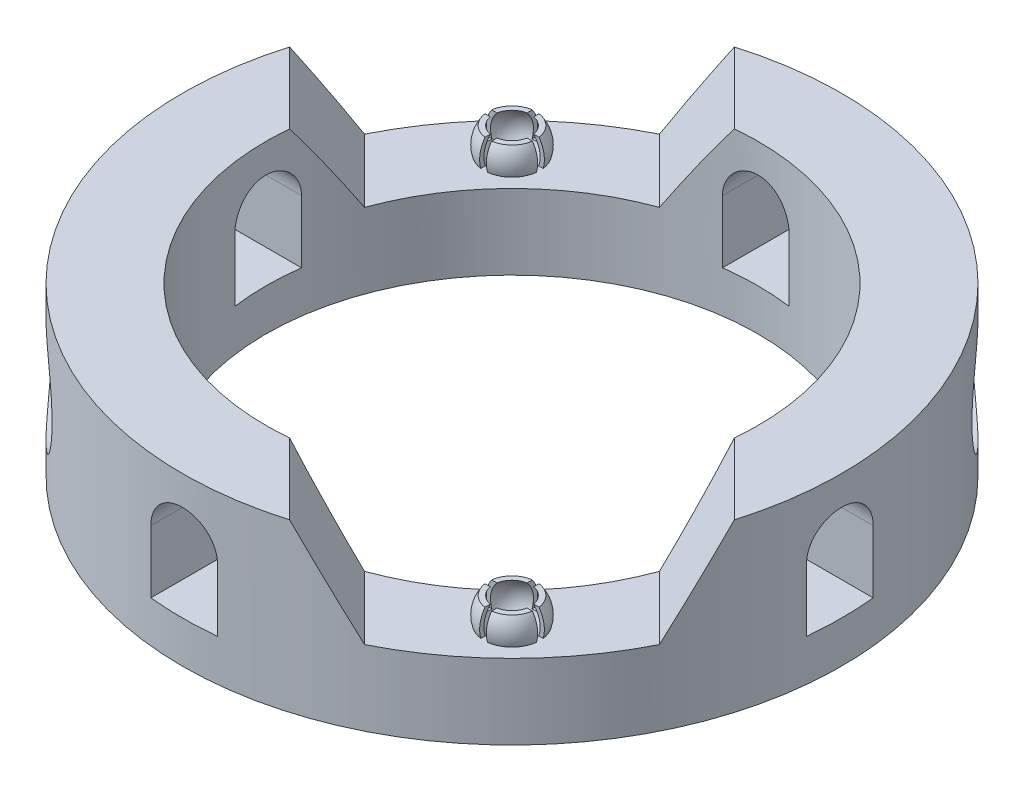
SolidWorks part; units mm, degrees
ref_plane "Front Plane" through (0, 0, 0) normal (0, 0, 1) x (1, 0, 0)
ref_plane "Top Plane" through (0, 0, 0) normal (0, 1, 0) x (1, 0, 0)
ref_plane "Right Plane" through (0, 0, 0) normal (1, 0, 0) x (0, 0, -1)
sketch "Sketch1" plane through (0, 0, 0) normal (0, 1, 0) x (1, 0, 0)
  circle A0 centre (0, 0) radius 29.5
  circle A1 centre (0, 0) radius 39.5
  dimension "D1" = 59
  dimension "D2" = 79
extrude "Boss-Extrude1" add sketch "Sketch1" along normal blind 20
ref_plane "Plane1" through (0, 0, 0) normal (0.7071, 0, -0.7071) x (-0.7071, 0, -0.7071)
sketch "Sketch2" plane through (0, 0, 0) normal (1, 0, 0) x (0, 0, -1)
  line L0 (0, 0) -> (0, 30.0667) construction
  line L1 (4, 5) -> (-4, 5)
  line L2 (-4, 5) -> (-4, 12.5)
  line L3 (4, 5) -> (4, 12.5)
  arc A0 (-4, 12.5) -> (4, 12.5) centre (0, 12.5) cw
  dimension "D6" = 4
  dimension "D1" = 8
  dimension "D2" = 4
  dimension "D3" = 5
  dimension "D4" = 7.5
  dimension "D5" = 7.5
extrude "Cut-Extrude1" cut sketch "Sketch2" against normal through all
extrude "Cut-Extrude2" cut sketch "Sketch2<2>" along normal through all
sketch "Sketch2<2>" plane through (0, 0, 0) normal (1, 0, 0) x (0, 0, -1) same geometry as "Sketch2"
mirror "Mirror1" about plane through (0, 0, 0) normal (0.7071, 0, -0.7071) of "Cut-Extrude2", "Cut-Extrude1"
sketch "Sketch4" plane through (0, 0, 0) normal (0.7071, 0, -0.7071) x (-0.7071, 0, -0.7071)
  line L0 (0, 0) -> (0, 44.1067) construction
  circle A0 centre (0, 10) radius 3.175
  dimension "D1" = 6.35
  dimension "D2" = 10
extrude "Cut-Extrude3" cut sketch "Sketch4" against normal up to next
extrude "Cut-Extrude4" cut sketch "Sketch4<2>" along normal up to next
sketch "Sketch4<2>" plane through (0, 0, 0) normal (0.7071, 0, -0.7071) x (-0.7071, 0, -0.7071) same geometry as "Sketch4"
ref_plane "Plane2" through (0, 0, 0) normal (0.7071, 0, 0.7071) x (0.7071, 0, -0.7071)
sketch "Sketch5" plane through (0, 20, 0) normal (0, 1, 0) x (1, 0, 0)
  line L0 (13.6827, -13.6827) -> (-13.6827, 13.6827) construction
  line L1 (-27.9307, 27.9307) -> (27.9307, -27.9307) construction
  line L2 (25.4558, -28.9914) -> (28.9914, -25.4558)
  line L3 (25.4558, -28.9914) -> (19.799, -23.3345)
  line L4 (28.9914, -25.4558) -> (23.3345, -19.799)
  line L5 (19.799, -23.3345) -> (23.3345, -19.799)
  line L6 (25.4558, -28.9914) -> (23.3345, -19.799) construction
  line L7 (28.9914, -25.4558) -> (19.799, -23.3345) construction
  circle A0 centre (0, 0) radius 39.5 construction
  circle A1 centre (0, 0) radius 29.5 construction
  point P7 (24.3952, -24.3952)
  dimension "D1" = 34.5
  dimension "D2" = 8
  dimension "D3" = 5
extrude "Boss-Extrude2" add sketch "Sketch5" along normal blind 13
sketch "Sketch6" plane through (1.7678, 0, -1.7678) normal (0.7071, 0, -0.7071) x (-0.7071, 0, -0.7071)
  line L0 (-38.5, 33) -> (-38.5, 20) construction
  line L1 (-38.5, 33) -> (-30.5, 33) construction
  line L2 (-30.5, 33) -> (-30.5, 20) construction
  line L4 (-38.5, 28) -> (-38.5, 33)
  line L8 (-38.5, 33) -> (-30.5, 33)
  line L9 (-30.5, 33) -> (-30.5, 28)
  arc A0 (-38.5, 28) -> (-30.5, 28) centre (-34.5, 28) cw
  dimension "D3" = 4
  dimension "D1" = 4
  dimension "D2" = 5
extrude "Cut-Extrude7" cut sketch "Sketch6" against normal up to next
sketch "Sketch7" plane through (1.7678, 0, -1.7678) normal (0.7071, 0, -0.7071) x (-0.7071, 0, -0.7071)
  circle A0 centre (-34.5, 28) radius 1
  dimension "D1" = 2
extrude "Cut-Extrude8" cut sketch "Sketch7" against normal up to next
ref_plane "Plane3" through (27.9307, 0, -27.9307) normal (0.7071, 0, -0.7071) x (-0.7071, 0, -0.7071)
sketch "Sketch8" plane through (27.9307, 0, -27.9307) normal (0.7071, 0, -0.7071) x (-0.7071, 0, -0.7071)
  circle A0 centre (0, 10) radius 6.35
  dimension "D1" = 12.7
extrude "Cut-Extrude9" cut sketch "Sketch8" against normal blind 1
mirror "Mirror3" about plane through (0, 0, 0) normal (0.7071, 0, -0.7071) of "Cut-Extrude9"
ref_plane "Plane4" through (0, 0, 0) normal (0.7071, 0, -0.7071) x (-0.7071, 0, -0.7071)
ref_plane "Plane5" through (0, 10, 0) normal (0, 1, 0) x (1, 0, 0)
ref_axis "Ball Join Axis" through (-41.2502, 10, -41.2502) along (0.7071, 0, 0.7071)
sketch "Sketch9" plane through (0, 20, 0) normal (0, 1, 0) x (1, 0, 0)
  line L3 (-17.6234, 26.1087) -> (-21.9323, 30.4175)
  line L4 (-26.1087, 17.6234) -> (-30.4175, 21.9323)
  line L5 (-41.2502, 41.2502) -> (45.8258, -45.8258) construction
  arc A0 (-17.6234, 26.1087) -> (-26.1087, 17.6234) centre (0, 0) ccw
  arc A1 (-21.9323, 30.4175) -> (-30.4175, 21.9323) centre (0, 0) ccw
  dimension "D3" = 37.5
  dimension "D4" = 31.5
  dimension "D1" = 6
  dimension "D2" = 6
extrude "Cut-Extrude11" cut sketch "Sketch9" against normal blind 15 contours A1 L4 A0 L3
sketch "Sketch10" plane through (0, 0, 0) normal (0.7071, 0, 0.7071) x (0.7071, 0, -0.7071)
  circle A0 centre (0, 10) radius 1.5
  dimension "D2" = 3
  dimension "D1" = 0
extrude "Cut-Extrude12" cut sketch "Sketch10" against normal blind 40
ref_plane "Plane8" through (0, 35, 0) normal (0, 1, 0) x (1, 0, 0)
sketch "Sketch15" plane through (0, 35, 0) normal (0, 1, 0) x (1, 0, 0)
  line L0 (-17.6564, 35.3341) -> (-10.0556, 27.7333)
  line L1 (-35.3341, 17.6564) -> (-27.7333, 10.0556)
  line L2 (10.0556, -27.7333) -> (17.6564, -35.3341)
  line L3 (27.7333, -10.0556) -> (35.3341, -17.6564)
  line L4 (-41.2502, 41.2502) -> (45.8258, -45.8258) construction
  arc A0 (17.6564, -35.3341) -> (35.3341, -17.6564) centre (0, 0) ccw
  arc A1 (-10.0556, 27.7333) -> (-27.7333, 10.0556) centre (0, 0) ccw
  arc A2 (-17.6564, 35.3341) -> (-35.3341, 17.6564) centre (0, 0) ccw
  arc A3 (10.0556, -27.7333) -> (27.7333, -10.0556) centre (0, 0) ccw
  dimension "D2" = 79
  dimension "D3" = 12.5
  dimension "D5" = 29.5
  dimension "D1" = 12.5
  dimension "D4" = 0
  dimension "0" = 0
extrude "Boss-Extrude3" add sketch "Sketch15" against normal through all contours A3 L2 A0 L3 | A1 L1 A2 L0 region at (23.8265, 35, 23.8265)
ref_plane "Plane9" through (0, 9, 0) normal (0, -1, 0) x (-1, 0, 0)
extrude "Cut-Extrude14" cut sketch "Sketch15<5>" against normal up to surface (26 mm away) contours A3 L2 A0 L3 | A2 L1 A1 L0 region at (23.8265, 35, 23.8265) up to plane "Plane9"
sketch "Sketch15<5>" plane through (0, 35, 0) normal (0, 1, 0) x (1, 0, 0) same geometry as "Sketch15"
ref_plane "Plane10" through (0, 10, 0) normal (0, 1, 0) x (1, 0, 0)
sketch "Sketch17" plane through (0, 10, 0) normal (0, 1, 0) x (1, 0, 0)
  line L5 (-41.2502, 41.2502) -> (45.8258, -45.8258) construction
  point P0 (-24.3952, 24.3952)
  point P1 (24.3952, -24.3952)
  point P4 (0, 0)
  dimension "D1" = 34.5
  dimension "D2" = 0
  dimension "D3" = 0
  dimension "D4" = 34.5
sketch "Sketch18" plane through (0, 10, 0) normal (0, 1, 0) x (1, 0, 0)
  line L0 (-24.3952, 27.8952) -> (-24.3952, 20.8952)
  line L1 (24.3952, -20.8952) -> (24.3952, -27.8952)
  arc A0 (-24.3952, 20.8952) -> (-24.3952, 27.8952) centre (-24.3952, 24.3952) ccw
  arc A1 (24.3952, -27.8952) -> (24.3952, -20.8952) centre (24.3952, -24.3952) ccw
revolve "Cut-Revolve1" cut sketch "Sketch18" angle 360 about L0 region at (-22.9097, 10, -24.3952)
revolve "Cut-Revolve2" cut sketch "Sketch18<3>" angle 360 about L1 region at (25.8806, 10, 24.3952)
sketch "Sketch18<3>" plane through (0, 10, 0) normal (0, 1, 0) x (1, 0, 0) same geometry as "Sketch18"
chamfer "Chamfer2" distance 11 angle 30 2 edges at (-31.5337, 20, -13.856) (13.856, 20, 31.5337) first distance on face at (-31.5337, 14.5, -13.856) first distance on face at (13.856, 14.5, 31.5337)
chamfer "Chamfer3" distance 11 angle 30 2 edges at (31.5337, 20, 13.856) (-13.856, 20, -31.5337) first distance on face at (31.5337, 14.5, 13.856) first distance on face at (-13.856, 14.5, -31.5337)
sketch "Sketch21" plane through (0, 0, 0) normal (0.7071, 0, -0.7071) x (-0.7071, 0, -0.7071)
  line L0 (-34.5, 13.5) -> (-34.5, 13)
  line L1 (-34.5, 7) -> (-34.5, 6.5)
  arc A0 (-34.5, 6.5) -> (-34.5, 13.5) centre (-34.5, 10) ccw
  arc A1 (-34.5, 7) -> (-34.5, 13) centre (-34.5, 10) ccw
  dimension "D1" = 3.5
revolve "Revolve1" add sketch "Sketch21" angle 360 about L0
ref_plane "Plane11" through (0, 12, 0) normal (0, 1, 0) x (1, 0, 0)
sketch "Sketch24" plane through (0, 12, 0) normal (0, 1, 0) x (1, 0, 0)
  circle A0 centre (24.3952, -24.3952) radius 3.5
  dimension "D1" = 0
extrude "Cut-Extrude15" cut sketch "Sketch24" along normal through all
sketch "Sketch26" plane through (0, 12, 0) normal (0, 1, 0) x (1, 0, 0)
  line L0 (23.9952, -24.7952) -> (23.9952, -27.8952)
  line L1 (20.9181, -23.9952) -> (23.9952, -23.9952)
  line L3 (20.9181, -24.7952) -> (23.9952, -24.7952)
  line L6 (23.9952, -20.9181) -> (23.9952, -23.9952)
  line L7 (23.9952, -27.8952) -> (24.7952, -27.8952)
  line L8 (24.7952, -20.9181) -> (24.7952, -23.9952)
  line L9 (24.7952, -23.9952) -> (27.8723, -23.9952)
  line L10 (24.7952, -24.7952) -> (24.7952, -27.8952)
  line L11 (24.7952, -24.7952) -> (27.8723, -24.7952)
  arc A2 (24.7952, -20.9181) -> (23.9952, -20.9181) centre (24.3952, -24.3952) ccw
  arc A3 (20.9181, -23.9952) -> (20.9181, -24.7952) centre (24.3952, -24.3952) ccw
  arc A4 (27.8723, -24.7952) -> (27.8723, -23.9952) centre (24.3952, -24.3952) ccw
  arc A5 (23.9952, -27.8952) -> (24.7952, -27.8952) centre (24.3952, -24.3952) ccw
  point P4 (24.3952, -27.8952)
  point P5 (27.8952, -24.3952)
  point P12 (20.8952, -24.3952)
  point P13 (0, 0)
  point P14 (24.3952, -20.8952)
  circle M10 centre (24.3952, -24.3952) radius 2.2361
  circle M11 centre (24.3952, -24.3952) radius 2.8723
  dimension "D1" = 7
  dimension "D6" = 0.4
  dimension "D2" = 7
  dimension "D3" = 3.5
  dimension "D4" = 0.8
  dimension "D5" = 0.4
  dimension "D7" = 0.8
  dimension "D8" = 3.5
extrude "Cut-Extrude18" cut sketch "Sketch26" against normal up to surface (3 mm away) contours L1 A3 L3 M11 | L3 L1 M11 M10 | L10 L11 L9 L8 L6 L1 L3 L0 M10 | L8 L6 M11 M10 | L8 A2 L6 M11 | L11 L9 M10 M11 | L11 A4 L9 M11 | L10 L0 L7 M11 | L10 L0 M10 M11 region at (24.3952, 12, 24.3952) region at (24.3952, 12, 26.9387) region at (21.8517, 12, 24.3952) region at (24.3952, 12, 27.5766) region at (21.2175, 12, 24.3952) region at (26.9387, 12, 24.3952) region at (24.3952, 12, 21.8517) region at (27.5728, 12, 24.3952) region at (24.3952, 12, 21.2175) up to face at (24.3952, 9, 21.0411)
ref_plane "Plane12" through (0, 0, 0) normal (0.7071, 0, 0.7071) x (0.7071, 0, -0.7071)
mirror "Mirror5" about plane through (0, 0, 0) normal (0.7071, 0, 0.7071) of "Cut-Extrude18", "Revolve1", "Cut-Extrude15"
